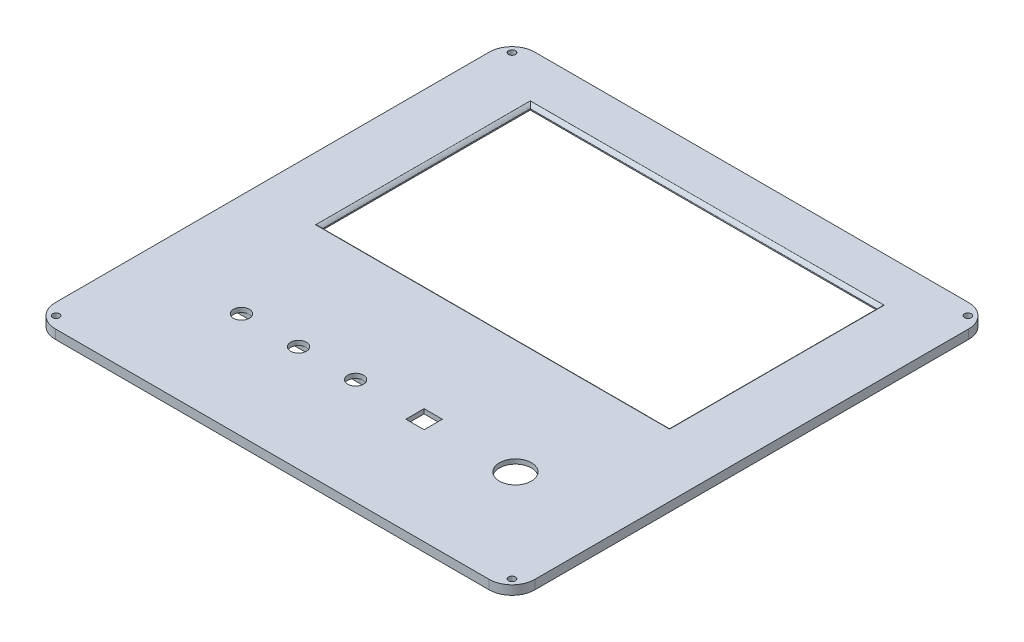
SolidWorks part; units mm, degrees
ref_plane "Front Plane" through (0, 0, 0) normal (0, 0, 1) x (1, 0, 0)
ref_plane "Top Plane" through (0, 0, 0) normal (0, 1, 0) x (1, 0, 0)
ref_plane "Right Plane" through (0, 0, 0) normal (1, 0, 0) x (0, 0, -1)
sketch "Sketch1" plane through (0, 0, 0) normal (0, 1, 0) x (1, 0, 0)
  line L0 (-101, -101) -> (-101, 101)
  line L5 (-105, -105) -> (105, -105)
  line L6 (-105, -105) -> (-105, 105)
  line L7 (-105, 105) -> (105, 105)
  line L8 (105, -105) -> (105, 105)
  line L9 (-101, 101) -> (101, 101)
  line L10 (101, -101) -> (101, 101)
  line L11 (-101, -101) -> (101, -101)
  line L12 (-101, 101) -> (-99.8333, 99.8333) construction
  line L13 (-55, 0) -> (55, 0) construction
  line L14 (-101, -101) -> (-99.8333, -99.8333) construction
  line L15 (0, -55) -> (0, 55) construction
  line L16 (101, -101) -> (99.8333, -99.8333) construction
  line L17 (101, 101) -> (99.8333, 99.8333) construction
  circle A1 centre (-99.8333, 99.8333) radius 1.5
  circle A2 centre (-99.8333, -99.8333) radius 1.5
  circle A3 centre (99.8333, -99.8333) radius 1.5
  circle A4 centre (99.8333, 99.8333) radius 1.5
  point P0 (0, 0)
  point P6 (-105, 0)
  point P7 (0, 105)
  dimension "D3" = 4
  dimension "D4" = 3
  dimension "D1" = 210
  dimension "D2" = 210
  dimension "D5" = 1.65
  dimension "D6" = 45
extrude "MainExtrude" add sketch "Sketch1" along normal blind 4 contours L6 L5 L8 L7
extrude "ScrewHoles" cut sketch "Sketch1<6>" along normal up to surface (4 mm away) contours A1 | A2 | A3 | A4 up to face at (0, 4, 0)
sketch "Sketch1<6>" plane through (0, 0, 0) normal (0, 1, 0) x (1, 0, 0) same geometry as "Sketch1"
fillet "RoundedCorners" radius 10 4 edges at (-105, 2, -105) (-105, 2, 105) (105, 2, -105) (105, 2, 105)
sketch "ScreenWindowSketch" plane through (0, 0, 0) normal (0, 1, 0) x (1, 0, 0)
  line L0 (0, 0) -> (0, 38.5) construction
  line L1 (-76, -7) -> (76, -7)
  line L2 (-76, -7) -> (-76, 84)
  line L3 (-76, 84) -> (76, 84)
  line L4 (76, -7) -> (76, 84)
  line L5 (-76, -7) -> (76, 84) construction
  line L6 (-76, 84) -> (76, -7) construction
  line L7 (-83, -14.5) -> (83, -14.5) construction
  line L8 (-83, -14.5) -> (-83, 91.5) construction
  line L9 (-83, 91.5) -> (83, 91.5) construction
  line L10 (83, -14.5) -> (83, 91.5) construction
  line L11 (-83, -14.5) -> (83, 91.5) construction
  line L12 (-83, 91.5) -> (83, -14.5) construction
  line L13 (0, 38.5) -> (0, 105) construction
  line L14 (-95, 105) -> (95, 105) construction
  point P6 (0, 38.5)
  dimension "D1" = 152
  dimension "D2" = 91
  dimension "D3" = 166
  dimension "D4" = 106
  dimension "D5" = 7.5
  dimension "D6" = 13.5
  dimension "D7" = 7.5
extrude "ScreenWindowCut" cut sketch "ScreenWindowSketch" along normal blind 10
sketch "ScreenDimensionsSketch" plane through (0, 0, 0) normal (0, 1, 0) x (1, 0, 0)
  line L0 (0, 0) -> (0, 38.5) construction
  line L1 (-76, -7) -> (76, -7) construction
  line L2 (-76, -7) -> (-76, 84) construction
  line L3 (-76, 84) -> (76, 84) construction
  line L4 (76, -7) -> (76, 84) construction
  line L5 (-76, -7) -> (76, 84) construction
  line L6 (-76, 84) -> (76, -7) construction
  line L7 (-83, -14.5) -> (83, -14.5)
  line L8 (-83, -14.5) -> (-83, 91.5)
  line L9 (-83, 91.5) -> (83, 91.5)
  line L10 (83, -14.5) -> (83, 91.5)
  line L11 (-83, -14.5) -> (83, 91.5) construction
  line L12 (-83, 91.5) -> (83, -14.5) construction
  line L13 (0, 38.5) -> (0, 105) construction
  line L15 (-95, 105) -> (95, 105) construction
  line L17 (-89, -17.5) -> (89, -17.5) construction
  line L18 (-89, -17.5) -> (-89, 94.5) construction
  line L19 (-89, 94.5) -> (89, 94.5) construction
  line L20 (89, -17.5) -> (89, 94.5) construction
  line L21 (-89, -17.5) -> (89, 94.5) construction
  line L22 (-89, 94.5) -> (89, -17.5) construction
  circle A0 centre (-89, 94.5) radius 3 construction
  circle A1 centre (-89, 94.5) radius 1.5 construction
  circle A2 centre (89, 94.5) radius 1.5 construction
  circle A3 centre (89, 94.5) radius 3 construction
  circle A4 centre (89, -17.5) radius 1.5 construction
  circle A5 centre (89, -17.5) radius 3 construction
  circle A6 centre (-89, -17.5) radius 1.5 construction
  circle A7 centre (-89, -17.5) radius 3 construction
  point P6 (0, 38.5)
  dimension "D8" = 3
  dimension "D9" = 6
  dimension "D1" = 152
  dimension "D2" = 91
  dimension "D3" = 166
  dimension "D4" = 106
  dimension "D5" = 7.5
  dimension "D6" = 13.5
  dimension "D7" = 7.5
  dimension "D10" = 6
  dimension "D11" = 3
extrude "ScreenDimensionCut" cut sketch "ScreenDimensionsSketch" along normal blind 2 from surface starting at face at (99.8333, 0, -101.3333)
fillet "ScreenRibbonCable" radius 20 1 edges at (0, 0, 14.5)
fillet "SmoothContactEdges" radius 1.5 4 edges at (-76, 4, -38.5) (0, 4, 7) (76, 4, -38.5) (0, 4, -84) conic radius 10
sketch "StandOffSketch" plane through (0, 0, 0) normal (0, 1, 0) x (1, 0, 0)
  line L0 (0, 0) -> (0, 39) construction
  line L1 (-76, -6.5) -> (76, -6.5) construction
  line L2 (-76, -6.5) -> (-76, 84.5) construction
  line L3 (-76, 84.5) -> (76, 84.5) construction
  line L4 (76, -6.5) -> (76, 84.5) construction
  line L5 (-76, -6.5) -> (76, 84.5) construction
  line L6 (-76, 84.5) -> (76, -6.5) construction
  line L7 (-83, -14) -> (83, -14) construction
  line L8 (-83, -14) -> (-83, 92) construction
  line L9 (-83, 92) -> (83, 92) construction
  line L10 (83, -14) -> (83, 92) construction
  line L11 (-83, -14) -> (83, 92) construction
  line L12 (-83, 92) -> (83, -14) construction
  line L13 (0, 39) -> (0, 105) construction
  line L14 (-95, 105) -> (95, 105) construction
  line L17 (-89, -17) -> (89, -17) construction
  line L18 (-89, -17) -> (-89, 95) construction
  line L19 (-89, 95) -> (89, 95) construction
  line L20 (89, -17) -> (89, 95) construction
  line L21 (-89, -17) -> (89, 95) construction
  line L22 (-89, 95) -> (89, -17) construction
  circle A0 centre (-89, 95) radius 3
  circle A1 centre (-89, 95) radius 1.5
  circle A2 centre (89, 95) radius 1.5
  circle A3 centre (89, 95) radius 3
  circle A4 centre (89, -17) radius 1.5
  circle A5 centre (89, -17) radius 3
  circle A6 centre (-89, -17) radius 1.5
  circle A7 centre (-89, -17) radius 3
  point P6 (0, 39)
  dimension "D8" = 3
  dimension "D9" = 6
  dimension "D12" = 178
  dimension "D1" = 152
  dimension "D2" = 91
  dimension "D3" = 166
  dimension "D4" = 106
  dimension "D5" = 7.5
  dimension "D6" = 13
  dimension "D7" = 7.5
  dimension "D10" = 6
  dimension "D11" = 3
  dimension "D13" = 112
extrude "StandOffExtrude" add sketch "StandOffSketch" against normal blind 2.25
sketch "HoleSketch" plane through (0, 0, 0) normal (0, 1, 0) x (1, 0, 0)
  line L0 (-60, -58.5) -> (-35, -58.5) construction
  line L1 (-35, -58.5) -> (-10, -58.5) construction
  line L2 (77.5, -8.5) -> (-77.5, -8.5) construction
  line L3 (16, -62.5) -> (24, -62.5)
  line L4 (16, -62.5) -> (16, -54.5)
  line L5 (16, -54.5) -> (24, -54.5)
  line L6 (24, -62.5) -> (24, -54.5)
  line L7 (16, -62.5) -> (24, -54.5) construction
  line L8 (16, -54.5) -> (24, -62.5) construction
  line L9 (-105, -95) -> (-105, 95) construction
  line L10 (105, -95) -> (105, 95) construction
  circle A0 centre (-60, -58.5) radius 3.45
  circle A1 centre (-35, -58.5) radius 3.45
  circle A2 centre (-10, -58.5) radius 3.45
  circle A3 centre (-60, -58.5) radius 7.5 construction
  circle A4 centre (-35, -58.5) radius 7.5 construction
  circle A5 centre (-10, -58.5) radius 7.5 construction
  circle A6 centre (60, -58.5) radius 7
  point P6 (20, -58.5)
  dimension "D1" = 6.9
  dimension "D2" = 15
  dimension "D3" = 14
  dimension "D4" = 8
  dimension "D5" = 50
  dimension "D6" = 45
  dimension "D7" = 25
  dimension "D8" = 30
  dimension "D9" = 45
extrude "HoleCut" cut sketch "HoleSketch" along normal through all
sketch "SpacingSketch" plane through (0, 0, 0) normal (0, -1, 0) x (1, 0, 0)
  line L0 (-60, 58.5) -> (-35, 58.5) construction
  line L1 (-35, 58.5) -> (-10, 58.5) construction
  line L2 (-105, 95) -> (-105, -95) construction
  line L3 (14, 52.5) -> (26, 52.5)
  line L4 (14, 52.5) -> (14, 64.5)
  line L5 (14, 64.5) -> (26, 64.5)
  line L6 (26, 52.5) -> (26, 64.5)
  line L7 (14, 52.5) -> (26, 64.5) construction
  line L8 (14, 64.5) -> (26, 52.5) construction
  line L9 (105, 95) -> (105, -95) construction
  line L11 (77.5, 8.5) -> (-77.5, 8.5) construction
  line L12 (-72.5, 61.95) -> (2.5, 61.95)
  line L13 (-72.5, 61.95) -> (-72.5, 55.05)
  line L14 (-72.5, 55.05) -> (2.5, 55.05)
  line L15 (2.5, 61.95) -> (2.5, 55.05)
  line L16 (-72.5, 61.95) -> (2.5, 55.05) construction
  line L17 (-72.5, 55.05) -> (2.5, 61.95) construction
  line L18 (-67.675, 61.95) -> (-52.325, 61.95)
  line L19 (-67.675, 61.95) -> (-67.675, 76.95)
  line L20 (-67.675, 76.95) -> (-52.325, 76.95)
  line L21 (-52.325, 61.95) -> (-52.325, 76.95)
  line L22 (-67.675, 61.95) -> (-52.325, 76.95) construction
  line L23 (-67.675, 76.95) -> (-52.325, 61.95) construction
  line L24 (-42.675, 61.95) -> (-27.325, 61.95)
  line L25 (-42.675, 61.95) -> (-42.675, 76.95)
  line L26 (-42.675, 76.95) -> (-27.325, 76.95)
  line L27 (-27.325, 61.95) -> (-27.325, 76.95)
  line L28 (-42.675, 61.95) -> (-27.325, 76.95) construction
  line L29 (-42.675, 76.95) -> (-27.325, 61.95) construction
  line L30 (-17.675, 61.95) -> (-2.325, 61.95)
  line L31 (-17.675, 61.95) -> (-17.675, 76.95)
  line L32 (-17.675, 76.95) -> (-2.325, 76.95)
  line L33 (-2.325, 61.95) -> (-2.325, 76.95)
  line L34 (-17.675, 61.95) -> (-2.325, 76.95) construction
  line L35 (-17.675, 76.95) -> (-2.325, 61.95) construction
  circle A0 centre (-60, 58.5) radius 3.45 construction
  circle A1 centre (-35, 58.5) radius 3.45 construction
  circle A2 centre (-10, 58.5) radius 3.45 construction
  circle A3 centre (-60, 58.5) radius 7.5 construction
  circle A4 centre (-35, 58.5) radius 7.5 construction
  circle A5 centre (-10, 58.5) radius 7.5 construction
  circle A6 centre (60, 58.5) radius 7 construction
  circle A7 centre (60, 58.5) radius 12.5
  point P6 (20, 58.5)
  point P20 (-60, 69.45)
  point P32 (-35, 61.95)
  point P37 (-10, 61.95)
  point P44 (-60, 61.95)
  point P48 (-35, 69.45)
  point P49 (-10, 69.45)
  dimension "D1" = 6.9
  dimension "D2" = 15
  dimension "D3" = 14
  dimension "D10" = 25
  dimension "D13" = 15.35
  dimension "D4" = 12
  dimension "D5" = 45
  dimension "D6" = 45
  dimension "D7" = 25
  dimension "D8" = 30
  dimension "D9" = 50
  dimension "D11" = 6.9
  dimension "D12" = 75
  dimension "D14" = 15
extrude "SpacingCut" cut sketch "SpacingSketch" against normal blind 2 contours L13 L12 L15 L14 | L19 L18 L21 L20 | L25 L24 L27 L26 | L31 L30 L33 L32 | L4 L3 L6 L5 | A7
